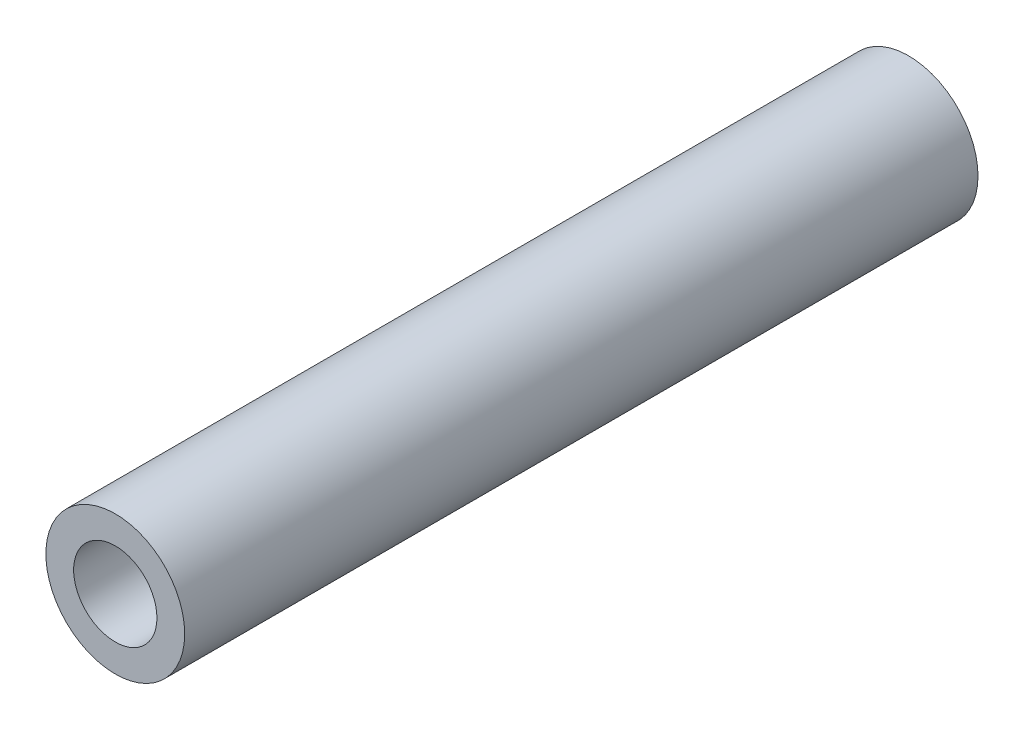
SolidWorks part; units mm, degrees
material "1060 Alloy"
ref_plane "Front Plane" through (0, 0, 0) normal (0, 0, 1) x (1, 0, 0)
ref_plane "Top Plane" through (0, 0, 0) normal (0, 1, 0) x (1, 0, 0)
ref_plane "Right Plane" through (0, 0, 0) normal (1, 0, 0) x (0, 0, -1)
sketch "Sketch1" plane through (0, 0, 0) normal (0, 0, 1) x (1, 0, 0)
  circle A0 centre (-93.2395, 27.2898) radius 2.1 construction
  circle A1 centre (-93.2395, 27.2898) radius 2.1
  circle A2 centre (-93.2395, 27.2898) radius 3.5
  dimension "D1" = 7
extrude "Boss-Extrude1" add sketch "Sketch1" along normal blind 40
